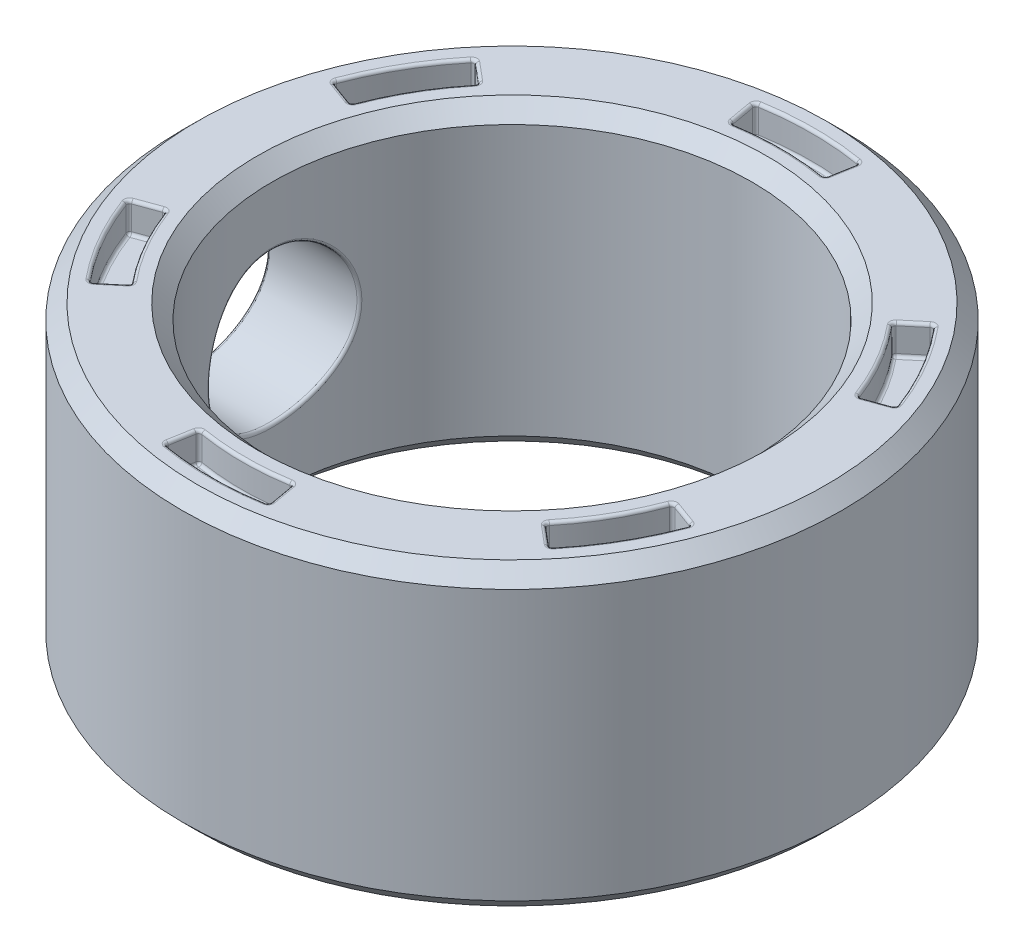
SolidWorks part; units mm, degrees
ref_plane "Front Plane" through (0, 0, 0) normal (0, 0, 1) x (1, 0, 0)
ref_plane "Top Plane" through (0, 0, 0) normal (0, 1, 0) x (1, 0, 0)
ref_plane "Right Plane" through (0, 0, 0) normal (1, 0, 0) x (0, 0, -1)
sketch "Sketch1" plane through (0, 0, 0) normal (0, 1, 0) x (1, 0, 0)
  circle A0 centre (0, 0) radius 11
  circle A1 centre (0, 0) radius 8
  dimension "D1" = 22
  dimension "D2" = 16
extrude "Boss-Extrude1" add sketch "Sketch1" along normal blind 10
chamfer "Chamfer1" distance 0.5 angle 45 4 edges at (0, 0, 8) (0, 0, 11) (0, 10, 11) (0, 10, 8)
sketch "Sketch2" plane through (0, 10, 0) normal (0, 1, 0) x (1, 0, 0)
  line L0 (0, 0) -> (0, 10) construction
  line L1 (0, 0) -> (1.7365, 9.8481) construction
  line L2 (0, 0) -> (-1.7365, 9.8481) construction
  line L3 (-1.7365, 9.8481) -> (-1.5628, 8.8633)
  line L4 (1.7365, 9.8481) -> (1.5628, 8.8633)
  circle A0 centre (0, 0) radius 10 construction
  circle A1 centre (0, 0) radius 9 construction
  arc A2 (1.7365, 9.8481) -> (-1.7365, 9.8481) centre (0, 0) ccw
  arc A3 (1.5628, 8.8633) -> (-1.5628, 8.8633) centre (0, 0) ccw
  dimension "D1" = 20
  dimension "D2" = 18
  dimension "D3" = 10
extrude "Cut-Extrude1" cut sketch "Sketch2" against normal blind 1
fillet "Fillet1" radius 0.1 12 edges at (1.7365, 9.5, -9.8481) (1.5628, 9.5, -8.8633) (1.6497, 10, -9.3557) (1.6497, 9, -9.3557) (-1.5628, 9.5, -8.8633) (-1.7365, 9.5, -9.8481) (-1.6497, 10, -9.3557) (-1.6497, 9, -9.3557) (0, 10, -10) (0, 9, -10) (0, 10, -9) (0, 9, -9)
pattern_circular "CirPattern1" count 6 over 360 about axis through (0, 10, 0) along (0, -1, 0) of "Cut-Extrude1", "Fillet1"
sketch "Sketch3" plane through (0, 0, 0) normal (1, 0, 0) x (0, 0, -1)
  line L1 (0, 10) -> (0, 0) construction
  line L2 (8.5, 10) -> (-8.5, 10) construction
  circle A0 centre (0, 5) radius 2.5
  dimension "D1" = 5
extrude "Cut-Extrude2" cut sketch "Sketch3" against normal up to next
fillet "Fillet2" radius 0.1 2 edges at (-7.6123, 5.4442, 2.4602) (-10.724, 5.504, 2.4487)
